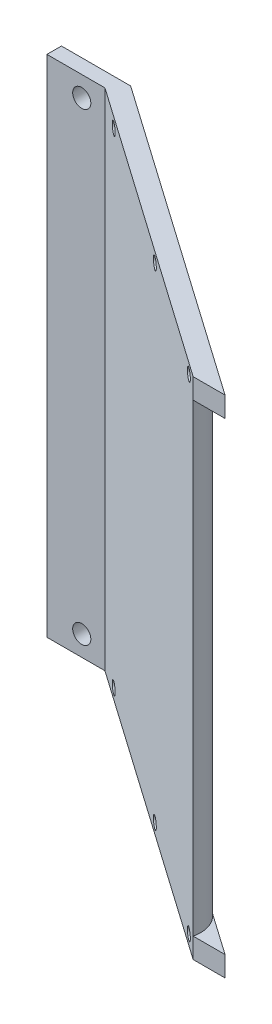
SolidWorks part; units mm, degrees
ref_plane "Front Plane" through (0, 0, 0) normal (0, 0, 1) x (1, 0, 0)
ref_plane "Top Plane" through (0, 0, 0) normal (0, 1, 0) x (1, 0, 0)
ref_plane "Right Plane" through (0, 0, 0) normal (1, 0, 0) x (0, 0, -1)
sketch "Sketch1" plane through (0, 0, 0) normal (0, 1, 0) x (1, 0, 0)
  line L0 (-113.9524, -17.3992) -> (-5.4132, -93.3992)
  line L1 (-137.8117, -17.3992) -> (-113.9524, -17.3992)
  line L2 (-137.8117, -17.3992) -> (-137.8117, -22.3992)
  line L3 (-137.8117, -22.3992) -> (-117.8117, -22.3992)
  line L5 (-117.8117, -22.3992) -> (-16.4132, -93.3992)
  line L7 (-16.4132, -93.3992) -> (-5.4132, -93.3992)
  dimension "D1" = 20
  dimension "D2" = 76
  dimension "D3" = 145
  dimension "D4" = 5
  dimension "D5" = 145
  dimension "D6" = 11
extrude "Boss-Extrude1" add sketch "Sketch1" along normal blind 160
fillet "Fillet4" radius 10 1 edges at (-5.4132, 80, 93.3992)
extrude "Boss-Extrude2" add sketch "Sketch1<2>" against normal blind 7
sketch "Sketch1<2>" plane through (0, 0, 0) normal (0, 1, 0) x (1, 0, 0) same geometry as "Sketch1"
extrude "Boss-Extrude3" add sketch "Sketch1<3>" along normal blind 7 from offset 160
sketch "Sketch1<3>" plane through (0, 0, 0) normal (0, 1, 0) x (1, 0, 0) same geometry as "Sketch1"
sketch "Sketch5" plane through (0, 0, 22.3992) normal (0, 0, 1) x (1, 0, 0)
  line L0 (-117.8117, 167) -> (-117.8117, -7) construction
  line L1 (-137.8117, -7) -> (-117.8117, -7) construction
  line L2 (-137.8117, 167) -> (-117.8117, 167) construction
  circle A0 centre (-125.8117, 0) radius 3.125
  circle A1 centre (-125.8117, 160) radius 3.125
  dimension "D1" = 6.25
  dimension "D4" = 6.25
  dimension "D2" = 8
  dimension "D3" = 7
  dimension "D5" = 8
  dimension "D6" = 7
extrude "Cut-Extrude4" cut sketch "Sketch5" against normal blind 4.7
sketch "Sketch6" plane through (-49.2831, 0, 70.3835) normal (-0.5736, 0, 0.8192) x (0.8192, 0, 0.5736)
  line L0 (40.1267, 160) -> (-83.658, 160)
  line L1 (-83.658, 167) -> (-83.658, -7) construction
  line L2 (49.1374, 167) -> (49.1374, 160) construction
  line L3 (40.1267, 0) -> (-83.658, 0)
  circle A0 centre (34.1374, 163.5) radius 2.025
  circle A1 centre (-13.6226, 163.5) radius 2.025
  circle A2 centre (-71.3826, 163.5) radius 2.025
  circle A3 centre (34.1374, -3.5) radius 2.025
  circle A4 centre (-13.6226, -3.5) radius 2.025
  circle A5 centre (-71.3826, -3.5) radius 2.025
  dimension "D1" = 4.05
  dimension "D3" = 4.05
  dimension "D6" = 4.05
  dimension "D7" = 4.05
  dimension "D8" = 4.05
  dimension "D9" = 4.05
  dimension "D2" = 15
  dimension "D4" = 47.76
  dimension "D5" = 57.76
extrude "Cut-Extrude5" cut sketch "Sketch6" against normal blind 7 contours A0 | A1 | A2 | A3 | A4 | A5 region at (-21.3193, 163.5, 89.9639) region at (-60.442, 163.5, 62.5699) region at (-107.7563, 163.5, 29.4401) region at (-21.3193, -3.5, 89.9639) region at (-60.442, -3.5, 62.5699) region at (-107.7563, -3.5, 29.4401)
